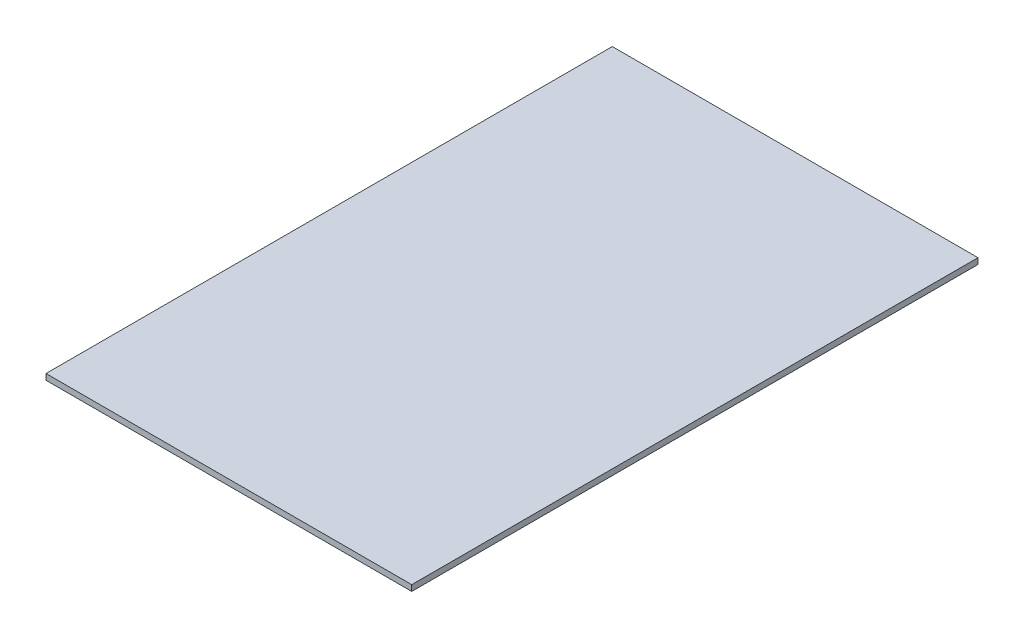
SolidWorks part; units mm, degrees
ref_plane "Front Plane" through (0, 0, 0) normal (0, 0, 1) x (1, 0, 0)
ref_plane "Top Plane" through (0, 0, 0) normal (0, 1, 0) x (1, 0, 0)
ref_plane "Right Plane" through (0, 0, 0) normal (1, 0, 0) x (0, 0, -1)
sketch "Sketch1" plane through (0, 0, 0) normal (0, 1, 0) x (1, 0, 0)
  line L1 (0, 0) -> (196.85, 0)
  line L2 (0, 0) -> (0, 304.8)
  line L3 (0, 304.8) -> (196.85, 304.8)
  line L4 (196.85, 0) -> (196.85, 304.8)
  dimension "D1" = 196.85
  dimension "D2" = 304.8
extrude "Boss-Extrude1" add sketch "Sketch1" along normal blind 3.175
